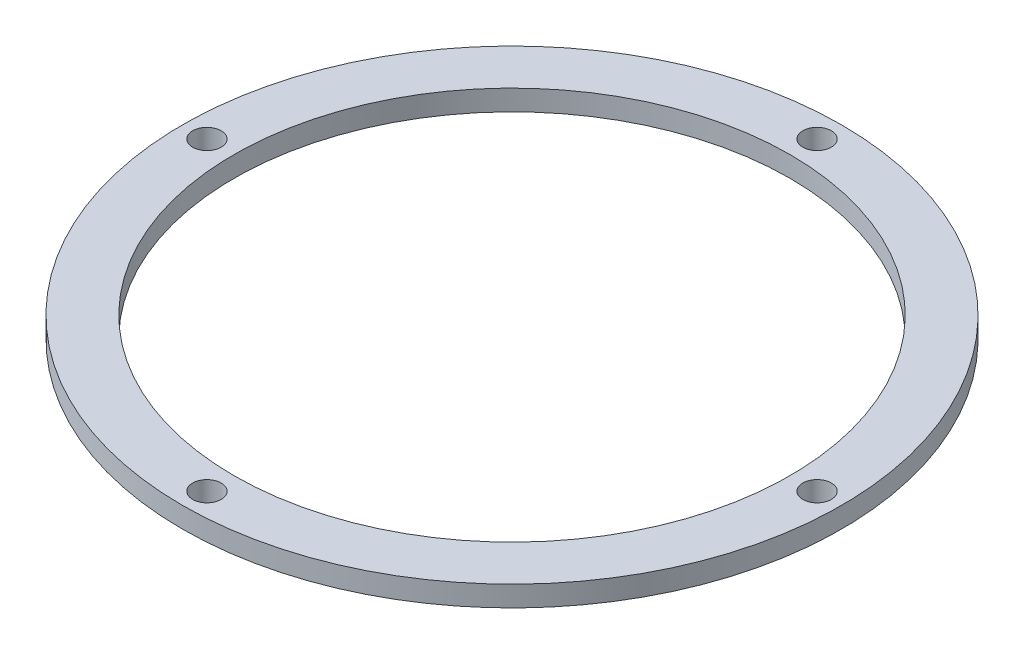
SolidWorks part; units mm, degrees
ref_plane "Front Plane" through (0, 0, 0) normal (0, 0, 1) x (1, 0, 0)
ref_plane "Top Plane" through (0, 0, 0) normal (0, 1, 0) x (1, 0, 0)
ref_plane "Right Plane" through (0, 0, 0) normal (1, 0, 0) x (0, 0, -1)
sketch "Sketch1" plane through (0, 0, 0) normal (0, 1, 0) x (1, 0, 0)
  circle A0 centre (0, 0) radius 101.6
  circle A1 centre (0, 0) radius 85.725
  circle A2 centre (0, 94.0452) radius 4.4
  circle A3 centre (94.0452, 0) radius 4.4
  circle A4 centre (0, -94.0452) radius 4.4
  circle A5 centre (-94.0452, 0) radius 4.4
  point P15 (0, 0)
  dimension "D1" = 203.2
  dimension "D2" = 15.875
  dimension "D3" = 8.8
  dimension "D4" = 94.0452
  dimension "D5" = 4
extrude "Boss-Extrude1" add sketch "Sketch1" along normal blind 6.35 contours A0 A1 region at (-98.7263, 0, 0)
